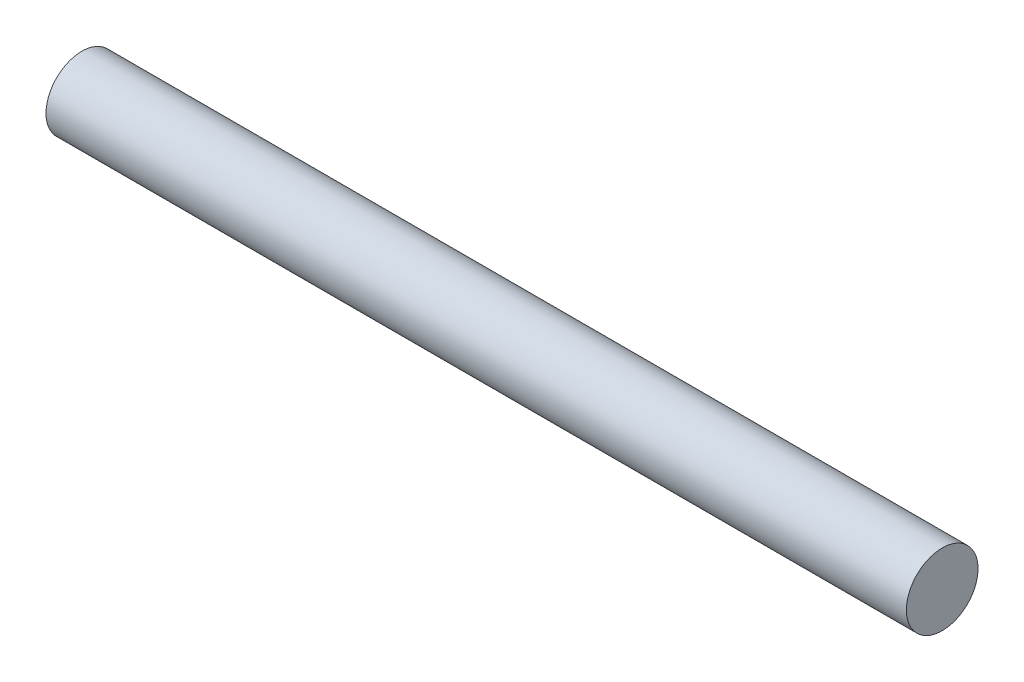
SolidWorks part; units mm, degrees
material "PLA"
ref_plane "Ebene vorne" through (0, 0, 0) normal (1, 0, 0) x (0, 1, 0)
ref_plane "Ebene oben" through (0, 0, 0) normal (0, 0, 1) x (0, 1, 0)
ref_plane "Ebene rechts" through (0, 0, 0) normal (0, 1, 0) x (-1, 0, 0)
sketch "Skizze1" plane through (0, 0, 0) normal (1, 0, 0) x (0, 1, 0)
  circle A0 centre (0, 0) radius 3.75
extrude "Aufsatz-Linear austragen1" add sketch "Skizze1" along normal blind 90
